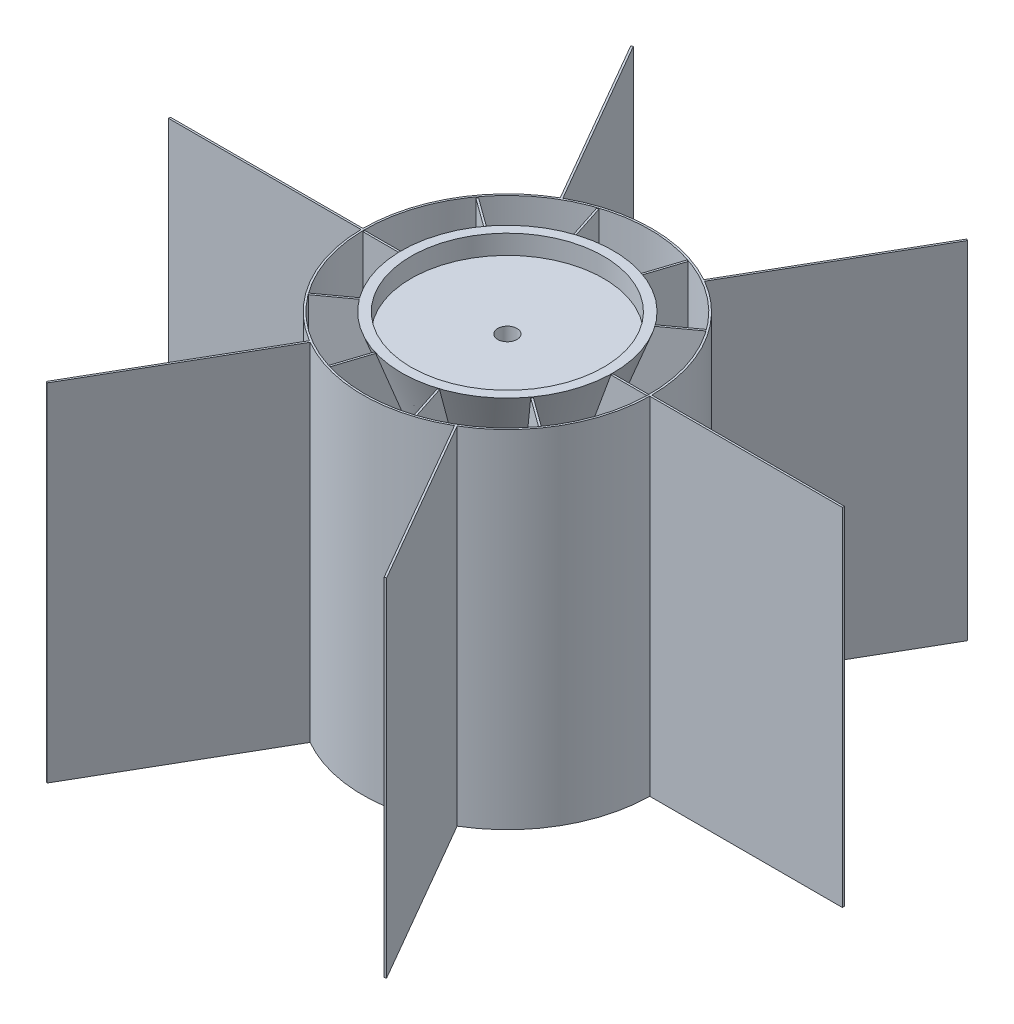
SolidWorks part; units mm, degrees
ref_plane "Front Plane" through (0, 0, 0) normal (0, 0, 1) x (1, 0, 0)
ref_plane "Top Plane" through (0, 0, 0) normal (0, 1, 0) x (1, 0, 0)
ref_plane "Right Plane" through (0, 0, 0) normal (1, 0, 0) x (0, 0, -1)
sketch "Sketch2" plane through (0, 0, 0) normal (0, 1, 0) x (1, 0, 0)
  circle A0 centre (0, 0) radius 75
  circle A1 centre (0, 0) radius 74
extrude "Boss-Extrude1" add sketch "Sketch2" along normal blind 180
ref_plane "Plane1" through (0, 180, 0) normal (0, 1, 0) x (1, 0, 0)
ref_plane "Plane2" through (0, 30, 0) normal (0, 1, 0) x (1, 0, 0)
sketch "Sketch3" plane through (0, 30, 0) normal (0, 1, 0) x (1, 0, 0)
  point P0 (0, 0)
sketch "Sketch4" plane through (0, 180, 0) normal (0, 1, 0) x (1, 0, 0)
  circle A0 centre (0, 0) radius 55
loft "Loft1" add profiles "Sketch4", "Sketch3"
ref_plane "Plane3" through (0, 105, 0) normal (0, 1, 0) x (1, 0, 0)
sketch "Sketch7" plane through (0, 105, 0) normal (0, 1, 0) x (1, 0, 0)
  line L0 (-74, 0) -> (-1.7013, 0)
  line L1 (-22.8673, 70.3782) -> (-0.5257, 1.618)
  line L2 (59.8673, 43.4961) -> (1.3764, 1)
  line L3 (59.8673, -43.4961) -> (1.3764, -1)
  line L4 (-22.8673, -70.3782) -> (-0.5257, -1.618)
  line L5 (-73.9932, -1) -> (-3.0777, -1)
  line L6 (-23.8162, 70.0627) -> (-1.9021, 2.618)
  line L7 (59.274, 44.3012) -> (1.9021, 2.618)
  line L8 (60.4496, -42.6831) -> (3.0777, -1)
  line L9 (-21.9141, -70.6808) -> (0, -3.2361)
  line L10 (-99.1947, -1) -> (106.1093, -1) construction
  line L11 (-99.1947, 0) -> (106.1093, 0) construction
  line L12 (0, -3.2361) -> (21.9141, -70.6808)
  line L15 (0.3249, -1) -> (1.3764, -1)
  line L16 (-1.3764, -1) -> (-59.8673, -43.4961)
  line L17 (-0.7265, -1) -> (-0.5257, -1.618)
  line L18 (-3.0777, -1) -> (-60.4496, -42.6831)
  line L19 (-1.3764, -1) -> (-0.7265, -1)
  line L21 (-1.1756, 0.382) -> (-1.7013, 0)
  line L22 (-1.3764, 1) -> (-59.8673, 43.4961)
  line L23 (-1.3764, 1) -> (-1.1756, 0.382)
  line L24 (-1.9021, 2.618) -> (-59.274, 44.3012)
  line L25 (0.3249, -1) -> (22.8673, -70.3782)
  line L26 (0.5257, 1.618) -> (0, 1.2361)
  line L27 (0, 1.2361) -> (-0.5257, 1.618)
  line L28 (0.5257, 1.618) -> (22.8673, 70.3782)
  line L29 (1.9021, 2.618) -> (23.8162, 70.0627)
  line L30 (1.1756, 0.382) -> (1.3764, 1)
  line L31 (1.7013, 0) -> (74, 0)
  line L32 (3.0777, -1) -> (73.9932, -1)
  line L33 (1.7013, 0) -> (1.1756, 0.382)
  circle A0 centre (0, 0) radius 27.5 construction
  arc A1 (-74, 0) -> (-73.9932, -1) centre (0, 0) ccw
  arc A2 (-60.4496, -42.6831) -> (-59.8673, -43.4961) centre (0, 0) ccw
  arc A3 (-59.274, 44.3012) -> (-59.8673, 43.4961) centre (0, 0) ccw
  arc A4 (-22.8673, 70.3782) -> (-23.8162, 70.0627) centre (0, 0) ccw
  arc A5 (23.8162, 70.0627) -> (22.8673, 70.3782) centre (0, 0) ccw
  arc A6 (59.8673, 43.4961) -> (59.274, 44.3012) centre (0, 0) ccw
  arc A7 (73.9932, -1) -> (74, 0) centre (0, 0) ccw
  arc A8 (59.8673, -43.4961) -> (60.4496, -42.6831) centre (0, 0) ccw
  arc A9 (21.9141, -70.6808) -> (22.8673, -70.3782) centre (0, 0) ccw
  arc A10 (-22.8673, -70.3782) -> (-21.9141, -70.6808) centre (0, 0) ccw
  point P18 (0, 0)
  point P29 (0, 0)
  dimension "D1" = 5
  dimension "D2" = 1
  dimension "D3" = 5
extrude "Boss-Extrude2" add sketch "Sketch7" along normal blind 74.5
sketch "Sketch8" plane through (0, 0, 0) normal (0, 1, 0) x (1, 0, 0)
  circle A0 centre (0, 0) radius 15
extrude "Boss-Extrude3" add sketch "Sketch8" along normal up to surface (70.9091 mm away) up to face at (13.297, 151.5625, 42.5421)
sketch "Sketch9" plane through (0, 0, 0) normal (1, 0, 0) x (0, 0, -1)
  circle A1 centre (0, 10) radius 3
extrude "Boss-Extrude4" add sketch "Sketch9" along normal up to surface (73.9392 mm away) up to face at (22.3909, 142.25, 70.5303)
sketch "Sketch10" plane through (0, 0, 0) normal (1, 0, 0) x (0, 0, -1)
  circle A1 centre (0, 10) radius 3
extrude "Boss-Extrude5" add sketch "Sketch10" against normal up to surface (73.9392 mm away) up to face at (0, 0, 74)
sketch "Sketch11" plane through (0, 0, 0) normal (0, 0, 1) x (1, 0, 0)
  circle A1 centre (0, 10) radius 3
extrude "Boss-Extrude6" add sketch "Sketch11" along normal up to surface (73.9392 mm away) up to face at (-73.9424, 9.3127, 2.9202)
sketch "Sketch12" plane through (0, 0, 0) normal (0, 0, 1) x (1, 0, 0)
  circle A1 centre (0, 10) radius 3
extrude "Boss-Extrude7" add sketch "Sketch12" against normal up to surface (73.9392 mm away) up to face at (73.9424, 9.3127, -2.9202)
hole_wizard "M12x1.5 Tapped Hole1" positions "Sketch13" profile "Sketch14" tap size "M12x1.5" standard "GB"
sketch "Sketch13" plane through (0, 0, 0) normal (0, -1, 0) x (-1, 0, 0)
  point P0 (0, 0)
sketch "Sketch14" plane through (0, 0, 0) normal (1, 0, 0) x (0, 0, -1)
  line L0 (0, 0) -> (0, 28.6545)
  line L1 (0, 28.6545) -> (5.25, 25.5)
  line L2 (5.25, 25.5) -> (5.25, 0.775)
  line L3 (5.25, 0.775) -> (6.025, 0)
  line L5 (6.025, 0) -> (0, 0)
  line L6 (-5.25, 0.775) -> (-6.025, 0) construction
  line L10 (0, 28.6545) -> (-5.25, 25.5) construction
  line L11 (0, -6.35) -> (0, 107.95) construction
  dimension "Tap Drill Dia." = 10.5
  dimension "Tap Drill Depth" = 25.5
  dimension "Near C'Sink Dia." = 12.05
  dimension "Near C'Sink Angle" = 90
  dimension "Drill Angle" = 118
cosmetic thread "Hole Thread1" parameters "D1"=18, "D2"=12
fillet "Fillet1" radius 10 1 edges at (0, 70.9091, 15)
fillet "Fillet2" radius 2 4 edges at (0.6233, 7.0655, -14.987) (14.7102, 10.6236, -2.9345) (-14.7102, 9.3764, 2.9345) (2.9345, 10.6236, 14.7102)
fillet "Fillet3" radius 2 4 edges at (2.9202, 9.3127, 73.9424) (73.9424, 9.3127, -2.9202) (0.6873, 7.0798, -73.9968) (-73.9424, 9.3127, 2.9202)
sketch "Sketch15" plane through (0, 0, 0) normal (0, 1, 0) x (1, 0, 0)
  line L0 (-175, 0) -> (-75, 0)
  line L1 (87.5, 151.5544) -> (37.5, 64.9519)
  line L2 (87.5, -151.5544) -> (37.5, -64.9519)
  line L3 (-174.9971, -1) -> (-74.9933, -1)
  line L4 (86.6325, 152.052) -> (36.6306, 65.4461)
  line L5 (88.3646, -151.052) -> (38.3627, -64.4461)
  line L6 (-110.7861, -1) -> (193.0391, -1) construction
  line L7 (-110.7861, 0) -> (193.0391, 0) construction
  line L10 (-38.3627, -64.4461) -> (-88.3646, -151.052)
  line L11 (-37.5, -64.9519) -> (-87.5, -151.5544)
  line L14 (74.9933, -1) -> (174.9971, -1)
  line L15 (75, 0) -> (175, 0)
  line L18 (-36.6306, 65.4461) -> (-86.6325, 152.052)
  line L19 (-37.5, 64.9519) -> (-87.5, 151.5544)
  arc A0 (-38.3627, -64.4461) -> (-37.5, -64.9519) centre (0, 0) ccw
  arc A1 (-175, 0) -> (-174.9971, -1) centre (0, 0) ccw
  arc A2 (-86.6325, 152.052) -> (-87.5, 151.5544) centre (0, 0) ccw
  arc A3 (87.5, 151.5544) -> (86.6325, 152.052) centre (0, 0) ccw
  arc A4 (174.9971, -1) -> (175, 0) centre (0, 0) ccw
  arc A5 (87.5, -151.5544) -> (88.3646, -151.052) centre (0, 0) ccw
  arc A6 (-88.3646, -151.052) -> (-87.5, -151.5544) centre (0, 0) ccw
  arc A7 (37.5, -64.9519) -> (38.3627, -64.4461) centre (0, 0) ccw
  arc A8 (74.9933, -1) -> (75, 0) centre (0, 0) ccw
  arc A9 (37.5, 64.9519) -> (36.6306, 65.4461) centre (0, 0) ccw
  arc A10 (-36.6306, 65.4461) -> (-37.5, 64.9519) centre (0, 0) ccw
  arc A11 (-75, 0) -> (-74.9933, -1) centre (0, 0) ccw
  point P12 (0, 0)
  point P20 (0, 0)
  dimension "D2" = 1
  dimension "D1" = 3
  dimension "D3" = 3
extrude "Boss-Extrude8" add sketch "Sketch15" along normal blind 180
sketch "Sketch19" plane through (0, 180, 0) normal (0, 1, 0) x (1, 0, 0)
  circle A0 centre (0, 0) radius 50
extrude "Cut-Extrude1" cut sketch "Sketch19" against normal blind 10
sketch "Sketch20" plane through (0, 180, 0) normal (0, 1, 0) x (1, 0, 0)
  circle A0 centre (0, 0) radius 5
extrude "Cut-Extrude2" cut sketch "Sketch20" against normal blind 180
